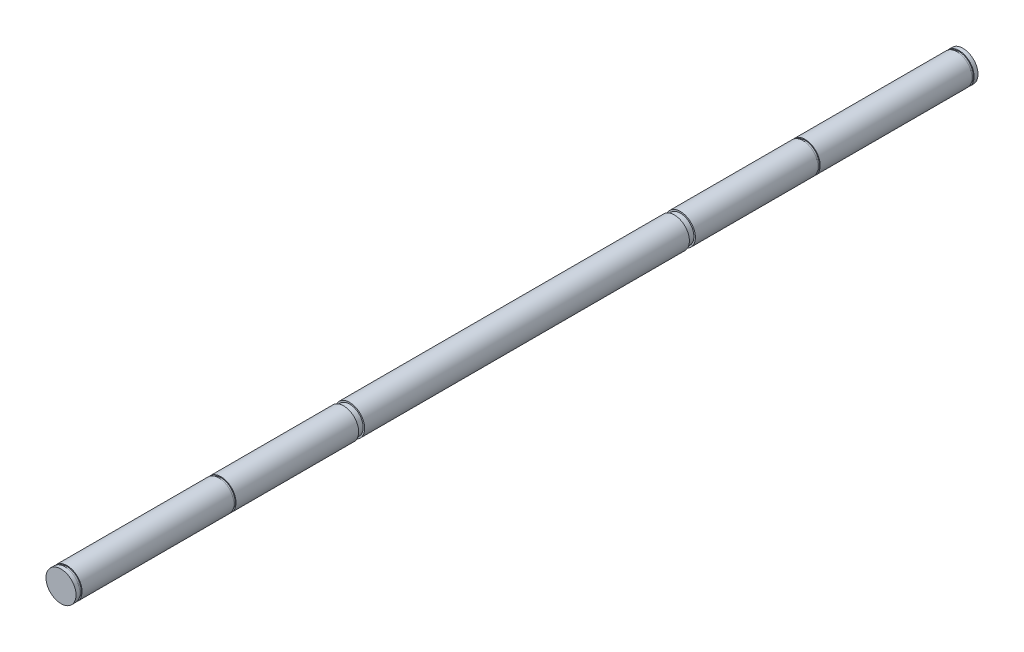
SolidWorks part; units mm, degrees
ref_plane "Front Plane" through (0, 0, 0) normal (0, 0, 1) x (1, 0, 0)
ref_plane "Top Plane" through (0, 0, 0) normal (0, 1, 0) x (1, 0, 0)
ref_plane "Right Plane" through (0, 0, 0) normal (1, 0, 0) x (0, 0, -1)
sketch "Sketch1" plane through (0, 0, 0) normal (0, 0, 1) x (1, 0, 0)
  circle A0 centre (0, 0) radius 5
  dimension "D1" = 10
extrude "Boss-Extrude1" add sketch "Sketch1" along normal mid plane 300
ref_plane "Plane1" through (0, 0, 148) normal (0, 0, 1) x (1, 0, 0)
ref_plane "Plane2" through (0, 0, 97.5) normal (0, 0, 1) x (1, 0, 0)
ref_plane "Plane3" through (0, 0, 55) normal (0, 0, 1) x (1, 0, 0)
sketch "Sketch2" plane through (0, 0, 148) normal (0, 0, 1) x (1, 0, 0)
  circle A0 centre (0, 0) radius 4.7
  circle A1 centre (0, 0) radius 5
  circle A2 centre (0, 0) radius 5
  dimension "D2" = 9.4
  dimension "D1" = 0
extrude "Cut-Extrude1" cut sketch "Sketch2" along normal blind 0.7
sketch "Sketch3" plane through (0, 0, 97.5) normal (0, 0, 1) x (1, 0, 0)
  circle A0 centre (0, 0) radius 5 construction
  circle A1 centre (0, 0) radius 4.7 construction
  circle A2 centre (0, 0) radius 5
  circle A3 centre (0, 0) radius 4.7
extrude "Cut-Extrude2" cut sketch "Sketch3" against normal blind 0.7
sketch "Sketch4" plane through (0, 0, 55) normal (0, 0, 1) x (1, 0, 0)
  circle A0 centre (0, 0) radius 4.5
  circle A1 centre (0, 0) radius 5
  circle A2 centre (0, 0) radius 5
  dimension "D2" = 9
  dimension "D1" = 0
extrude "Cut-Extrude3" cut sketch "Sketch4" against normal mid plane 2
mirror "Mirror1" about plane through (0, 0, 0) normal (0, 0, 1) of "Cut-Extrude3", "Cut-Extrude1", "Cut-Extrude2"
